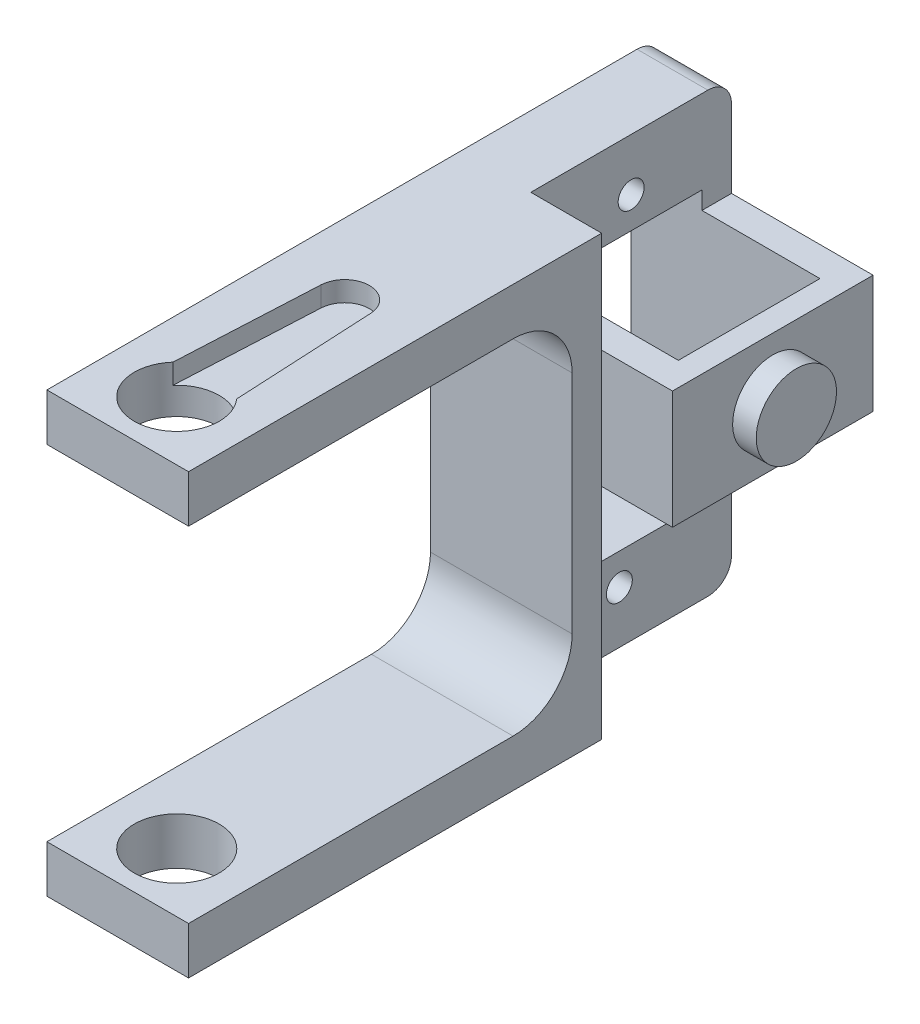
SolidWorks part; units mm, degrees
ref_plane "Front Plane" through (0, 0, 0) normal (0, 0, 1) x (1, 0, 0)
ref_plane "Top Plane" through (0, 0, 0) normal (0, 1, 0) x (1, 0, 0)
ref_plane "Right Plane" through (0, 0, 0) normal (1, 0, 0) x (0, 0, -1)
sketch "Sketch2" plane through (0, 0, 0) normal (0, 0, 1) x (1, 0, 0)
  line L1 (-8.6815, 2.0365) -> (3.3185, 2.0365)
  line L2 (-8.6815, 2.0365) -> (-8.6815, -35.1135)
  line L3 (-8.6815, -35.1135) -> (3.3185, -35.1135)
  line L4 (3.3185, 2.0365) -> (3.3185, -35.1135)
  line L13 (-8.6815, 2.0365) -> (3.3185, 2.0365)
  line L14 (-8.6815, 2.0365) -> (-8.6815, -1.9635)
  line L15 (-8.6815, -1.9635) -> (3.3185, -1.9635)
  line L16 (3.3185, 2.0365) -> (3.3185, -1.9635)
  line L21 (-8.6815, -35.1135) -> (3.3185, -35.1135)
  line L22 (-8.6815, -35.1135) -> (-8.6815, -31.1135)
  line L23 (-8.6815, -31.1135) -> (3.3185, -31.1135)
  line L24 (3.3185, -35.1135) -> (3.3185, -31.1135)
  dimension "D1" = 12
  dimension "D2" = 37.15
  dimension "D3" = 4
  dimension "D4" = 4
extrude "Boss-Extrude2" add sketch "Sketch2" along normal blind 35 contours L2 L15 L4 L1 | L22 L21 L24 L23 region at (-2.6815, 0.0365, 0)
extrude "Boss-Extrude3" add sketch "Sketch2<3>" along normal blind 2.5 contours L15 L2 L3 L4 region at (-2.6815, -16.5385, 0)
sketch "Sketch2<3>" plane through (0, 0, 0) normal (0, 0, 1) x (1, 0, 0) same geometry as "Sketch2"
sketch "Sketch7" plane through (0, 0, 0) normal (0, 0, -1) x (-1, 0, 0)
  line L5 (8.6815, -35.1135) -> (-3.3185, -35.1135) construction
  line L6 (8.6815, 2.0365) -> (2.6815, 2.0365)
  line L7 (8.6815, 2.0365) -> (8.6815, -35.1135)
  line L8 (8.6815, -35.1135) -> (2.6815, -35.1135)
  line L9 (2.6815, 2.0365) -> (2.6815, -35.1135)
extrude "Boss-Extrude4" add sketch "Sketch7" along normal blind 17
sketch "Sketch8" plane through (-2.6815, 0, 0) normal (1, 0, 0) x (0, 0, -1)
  line L0 (8.5, -5.0385) -> (8.5, 2.0365) construction
  line L1 (2.5, -5.0385) -> (14.5, -5.0385)
  line L2 (2.5, -5.0385) -> (2.5, -28.0385)
  line L3 (2.5, -28.0385) -> (14.5, -28.0385)
  line L4 (14.5, -5.0385) -> (14.5, -28.0385)
  line L5 (17, 2.0365) -> (0, 2.0365) construction
  line L6 (14.5, -16.5385) -> (17, -16.5385) construction
  line L7 (17, 2.0365) -> (17, -35.1135) construction
  circle A2 centre (8.5, -2.3885) radius 1.1
  circle A3 centre (7.5, -30.6885) radius 1.1
  dimension "D3" = 2.2
  dimension "D1" = 23
  dimension "D2" = 12
  dimension "D4" = 2.65
  dimension "D5" = 2.65
extrude "Cut-Extrude5" cut sketch "Sketch8" against normal up to next
sketch "Sketch9" plane through (0, 2.0365, 0) normal (0, 1, 0) x (1, 0, 0)
  line L0 (-0.5842, -15.6688) -> (0.0185, -27.6188)
  line L1 (-5.3815, -27.6188) -> (-4.7789, -15.6688)
  line L2 (-8.6815, -35) -> (3.3185, -35) construction
  line L3 (-2.6815, -30) -> (-2.6815, -35) construction
  arc A0 (-5.3815, -27.6188) -> (0.0185, -27.6188) centre (-2.6815, -30) ccw
  arc A1 (-0.5842, -15.6688) -> (-4.7789, -15.6688) centre (-2.6815, -15.7745) ccw
  dimension "D1" = 3.6
  dimension "D5" = 2.1
  dimension "D2" = 5
  dimension "D3" = 11.95
  dimension "D4" = 11.95
  dimension "D6" = 5.4
extrude "Cut-Extrude6" cut sketch "Sketch9" against normal blind 1.7
sketch "Sketch10" plane through (0, 2.0365, 0) normal (0, 1, 0) x (1, 0, 0)
  circle A0 centre (-2.6815, -30) radius 3.6
  dimension "D1" = 7.2
extrude "Cut-Extrude7" cut sketch "Sketch10" against normal through all
fillet "Fillet6" radius 5 1 edges at (-2.6815, -1.9635, 2.5)
fillet "Fillet7" radius 5 1 edges at (-2.6815, -31.1135, 2.5)
sketch "Sketch12" plane through (-2.6815, 0, 0) normal (1, 0, 0) x (0, 0, -1)
  line L0 (0, 2.0365) -> (0, -35.1135) construction
  line L1 (0, -6.5435) -> (2.5, -6.5435)
  line L2 (0, -6.5435) -> (0, -16.5435)
  line L3 (0, -16.5435) -> (2.5, -16.5435)
  line L4 (2.5, -6.5435) -> (2.5, -16.5435)
  line L5 (2.5, -5.0385) -> (2.5, -28.0385) construction
  line L6 (14.5, -28.0385) -> (14.5, -5.0385) construction
  line L7 (14.5, -6.5435) -> (17, -6.5435)
  line L8 (14.5, -6.5435) -> (14.5, -16.5435)
  line L9 (14.5, -16.5435) -> (17, -16.5435)
  line L10 (17, -6.5435) -> (17, -16.5435)
  line L11 (17, 2.0365) -> (17, -35.1135) construction
  line L14 (17, 2.0365) -> (0, 2.0365) construction
  dimension "D1" = 10
  dimension "D2" = 8.58
  dimension "D3" = 8.58
extrude "Boss-Extrude5" add sketch "Sketch12" along normal blind 10
sketch "Sketch13" plane through (7.3185, 0, 0) normal (1, 0, 0) x (0, 0, -1)
  line L1 (0, -6.5435) -> (17, -6.5435)
  line L2 (0, -6.5435) -> (0, -16.5435)
  line L3 (0, -16.5435) -> (17, -16.5435)
  line L4 (17, -6.5435) -> (17, -16.5435)
extrude "Boss-Extrude6" add sketch "Sketch13" along normal blind 2
sketch "Sketch14" plane through (9.3185, 0, 0) normal (1, 0, 0) x (0, 0, -1)
  line L0 (17, -6.5435) -> (0, -6.5435) construction
  line L3 (8.5, -11.5435) -> (8.5, -6.5435) construction
  line L4 (8.5, -11.5435) -> (17, -11.5435) construction
  line L5 (17, -16.5435) -> (17, -6.5435) construction
  circle A0 centre (8.5, -11.5435) radius 3.4
  dimension "D1" = 6.8
extrude "Boss-Extrude7" add sketch "Sketch14" along normal blind 2
fillet "Fillet8" radius 2 1 edges at (-5.6815, 2.0365, -17)
fillet "Fillet9" radius 2 1 edges at (-5.6815, -35.1135, -17)
